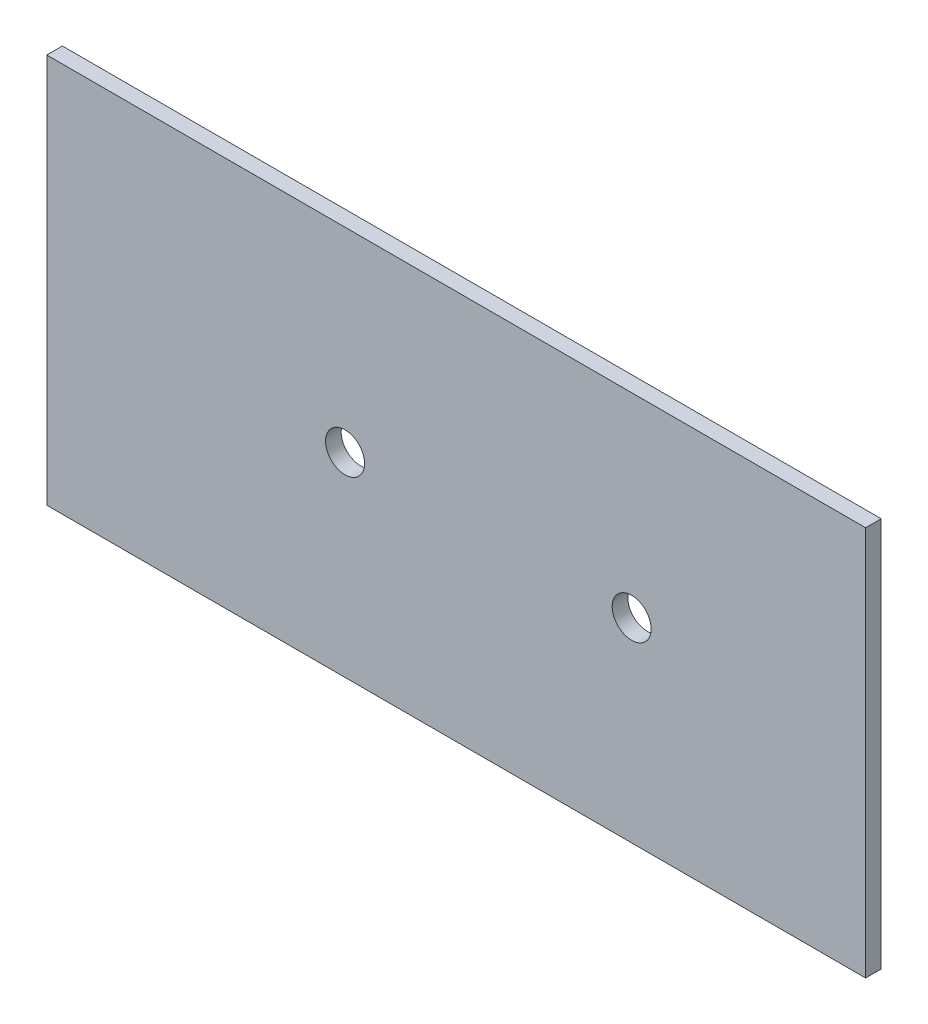
SolidWorks part; units mm, degrees
ref_plane "Front Plane" through (0, 0, 0) normal (0, 0, 1) x (1, 0, 0)
ref_plane "Top Plane" through (0, 0, 0) normal (0, 1, 0) x (1, 0, 0)
ref_plane "Right Plane" through (0, 0, 0) normal (1, 0, 0) x (0, 0, -1)
sketch "Sketch1" plane through (0, 0, 0) normal (0, 0, 1) x (1, 0, 0)
  line L1 (-150, -50) -> (60, -50)
  line L2 (-150, -50) -> (-150, 50)
  line L3 (-150, 50) -> (60, 50)
  line L4 (60, -50) -> (60, 50)
  circle A0 centre (0, 0) radius 5
  circle A2 centre (-73.5, 0) radius 5
  point P1 (0, 0)
  point P10 (0, 0)
  dimension "D3" = 10
  dimension "D4" = 0
  dimension "D1" = 150
  dimension "D2" = 100
  dimension "D8" = 73.5
  dimension "D9" = 60
extrude "Boss-Extrude1" add sketch "Sketch1" along normal blind 4
